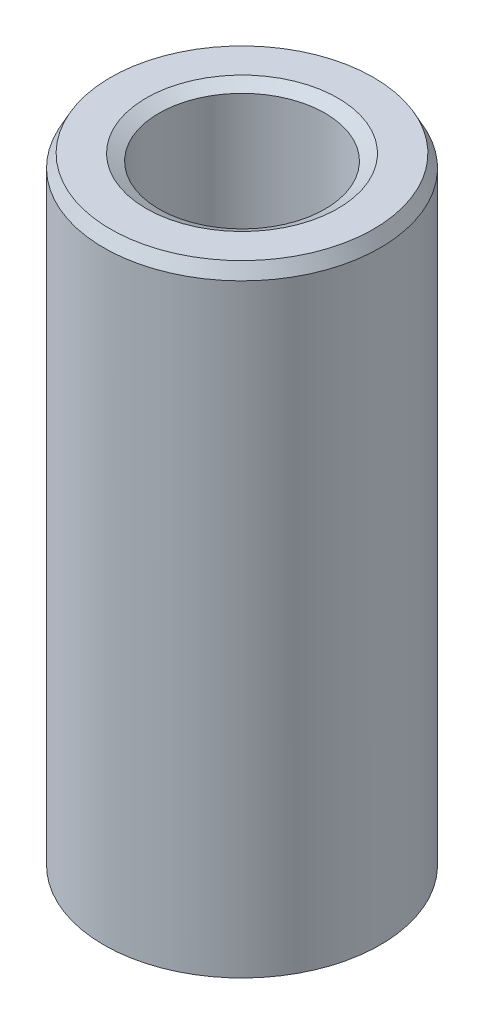
SolidWorks part; units mm, degrees
ref_plane "Front Plane" through (0, 0, 0) normal (0, 0, 1) x (1, 0, 0)
ref_plane "Top Plane" through (0, 0, 0) normal (0, 1, 0) x (1, 0, 0)
ref_plane "Right Plane" through (0, 0, 0) normal (1, 0, 0) x (0, 0, -1)
sketch "Sketch1" plane through (0, 0, 0) normal (0, 1, 0) x (1, 0, 0)
  circle A0 centre (0, 0) radius 20
  dimension "SLEEVE_OD" = 40
extrude "Boss-Extrude1" add sketch "Sketch1" along normal blind 90.1628
sketch "Sketch2" plane through (0, 0, 0) normal (0, 1, 0) x (1, 0, 0)
  circle A0 centre (0, 0) radius 12.0167
  dimension "BORE_D" = 24.0334
extrude "Cut-Extrude1" cut sketch "Sketch2" along normal through all
chamfer "Chamfer1" distance 1.8449 angle 27.991 4 edges at (0, 90.1628, 12.0167) (0, 0, 12.0167) (0, 0, 20) (0, 90.1628, 20) first distance on face at (0, 90.1628, 12.0167) first distance on face at (0, 0, 12.0167) first distance on face at (0, 90.1628, 20)
